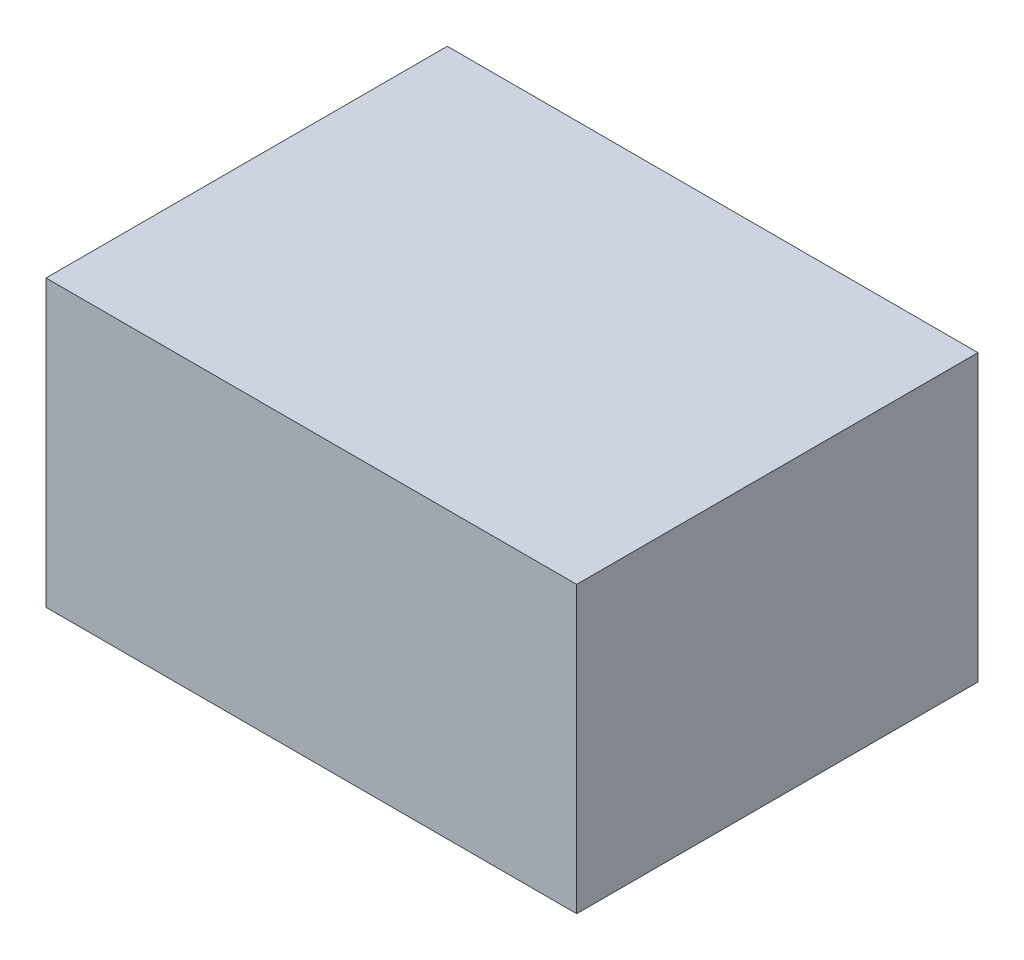
SolidWorks part; units mm, degrees
ref_plane "Front Plane" through (0, 0, 0) normal (0, 0, 1) x (1, 0, 0)
ref_plane "Top Plane" through (0, 0, 0) normal (0, 1, 0) x (1, 0, 0)
ref_plane "Right Plane" through (0, 0, 0) normal (1, 0, 0) x (0, 0, -1)
sketch "Sketch1" plane through (0, 0, 0) normal (0, 1, 0) x (1, 0, 0)
  line L1 (-160, -121) -> (160, -121)
  line L2 (-160, -121) -> (-160, 121)
  line L3 (-160, 121) -> (160, 121)
  line L4 (160, -121) -> (160, 121)
  line L5 (-160, -121) -> (160, 121) construction
  line L6 (-160, 121) -> (160, -121) construction
  point P0 (0, 0)
  dimension "D1" = 320
  dimension "D2" = 242
extrude "Boss-Extrude1" add sketch "Sketch1" along normal blind 172
equation "\"PCLength\"= 320mm'Length across I/O from PS to GPU"
equation "\"PCWidth\"= 242mm'Distance of longest part parallel to GPU(ussually GPU)"
equation "\"PCHeight\"= 172mm'Tallest point with mobo laying flat"
equation "\"WallThickness\"= 9mm'Thickness of each outer tank wall"
equation "\"ThermoBarrierThickness\"= 3mm'Thickness of barrier between hot side and cold side"
equation "\"HotSideGap\"= 35mm'Space in the hot side for a pump"
equation "\"PCClearance\"= 30mm'Clearance from top of tank to top of PC"
equation "\"RadiatorHeight\"= 275mm'Final Height from ground of radiators"
equation "\"D1@Sketch1\"=\"PCLength\""
equation "\"D2@Sketch1\"=\"PCWidth\""
equation "\"D1@Boss-Extrude1\"=\"PCHeight\""
